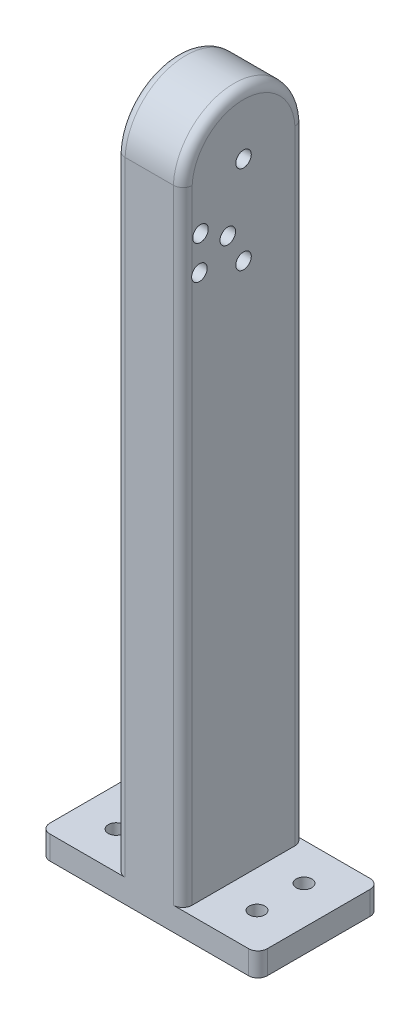
SolidWorks part; units mm, degrees
ref_plane "Front Plane" through (0, 0, 0) normal (0, 0, 1) x (1, 0, 0)
ref_plane "Top Plane" through (0, 0, 0) normal (0, 1, 0) x (1, 0, 0)
ref_plane "Right Plane" through (0, 0, 0) normal (1, 0, 0) x (0, 0, -1)
ref_plane "Plane1" through (23.135, 0, 0) normal (1, 0, 0) x (0, 0, -1)
sketch "Sketch1" plane through (23.135, 0, 0) normal (1, 0, 0) x (0, 0, -1)
  line L0 (3.3698, -169) -> (3.3698, -31.3252)
  line L1 (-22.5, -31.3252) -> (-22.5, -169)
  line L2 (-22.5, -169) -> (3.3698, -169)
  arc A0 (3.3698, -31.3252) -> (-22.5, -31.3252) centre (-9.5651, -31.95) ccw
extrude "Boss-Extrude1" add sketch "Sketch1" against normal blind 46.27
sketch "Sketch2" plane through (-23.135, 0, 0) normal (-1, 0, 0) x (0, 0, 1)
  line L0 (-3.3698, -31.3252) -> (-3.3698, -164)
  line L1 (-3.3698, -164) -> (22.5, -164)
  line L2 (22.5, -164) -> (22.5, -31.3252)
  arc A0 (22.5, -31.3252) -> (-3.3698, -31.3252) centre (9.5651, -31.95) ccw
extrude "Cut-Extrude1" cut sketch "Sketch2" against normal blind 16
ref_plane "Plane2" through (0, -164, 0) normal (0, -1, 0) x (1, 0, 0)
sketch "Sketch3" plane through (0, -164, 0) normal (0, -1, 0) x (1, 0, 0)
  line L0 (23.135, 22.5) -> (7.135, 22.5)
  line L1 (7.135, 22.5) -> (7.135, -3.3698)
  line L2 (7.135, -3.3698) -> (23.135, -3.3698)
  line L3 (23.135, -3.3698) -> (23.135, 22.5)
extrude "Cut-Extrude2" cut sketch "Sketch3" against normal through all
hole_wizard "Ø3.3 (3.3) Diameter Hole2" positions "Sketch7" profile "Sketch6" hole size "Ø3.3" standard "ANSI Metric"
sketch "Sketch7" plane through (7.135, 0, 0) normal (1, 0, 0) x (0, 0, -1)
  point P0 (-9.5651, -31.95)
  point P1 (-12.9168, -44.4587)
  point P2 (-9.5651, -50.725)
  point P3 (-18.9526, -48.2096)
  point P4 (-18.7221, -41.107)
sketch "Sketch6" plane through (7.135, -31.95, 9.5651) normal (0, 1, 0) x (0, 0, -1)
  line L0 (0, 0) -> (0, 30.27)
  line L1 (0, 30.27) -> (1.65, 30.27)
  line L2 (1.65, 30.27) -> (1.65, 0)
  line L5 (1.65, 0) -> (0, 0)
  line L11 (0, -6.35) -> (0, 107.95) construction
  dimension "Thru Hole Dia." = 3.3
  dimension "Thru Hole Depth" = 30.27
fillet "Fillet1" radius 2 10 edges at (23.135, -166.5, -3.3698) (-7.135, -97.6626, 22.5) (-7.135, -97.6626, -3.3698) (-7.135, -19, 9.5651) (-23.135, -166.5, -3.3698) (7.135, -97.6626, -3.3698) (7.135, -19, 9.5651) (7.135, -97.6626, 22.5) (23.135, -166.5, 22.5) (-23.135, -166.5, 22.5) tangent propagation no
sketch "Sketch9" plane through (0, -164, 0) normal (0, 1, 0) x (1, 0, 0)
  line L0 (-23.135, -9.5651) -> (-7.135, -9.5651) construction
  line L1 (-23.135, 1.3698) -> (-23.135, -20.5) construction
  line L2 (-7.135, 1.3698) -> (-7.135, -20.5) construction
  line L3 (0, 3.3698) -> (0, -22.5) construction
  line L4 (-5.135, 3.3698) -> (5.135, 3.3698) construction
  line L5 (-5.135, -22.5) -> (5.135, -22.5) construction
  circle A4 centre (-15, -4.5669) radius 1.65
  circle A5 centre (-15, -14.5633) radius 1.65
  circle A6 centre (15, -14.5633) radius 1.65
  circle A7 centre (15, -4.5669) radius 1.65
  dimension "D1" = 3.3
  dimension "D2" = 4.9982
  dimension "D3" = 30
extrude "Cut-Extrude4" cut sketch "Sketch9" against normal through all
